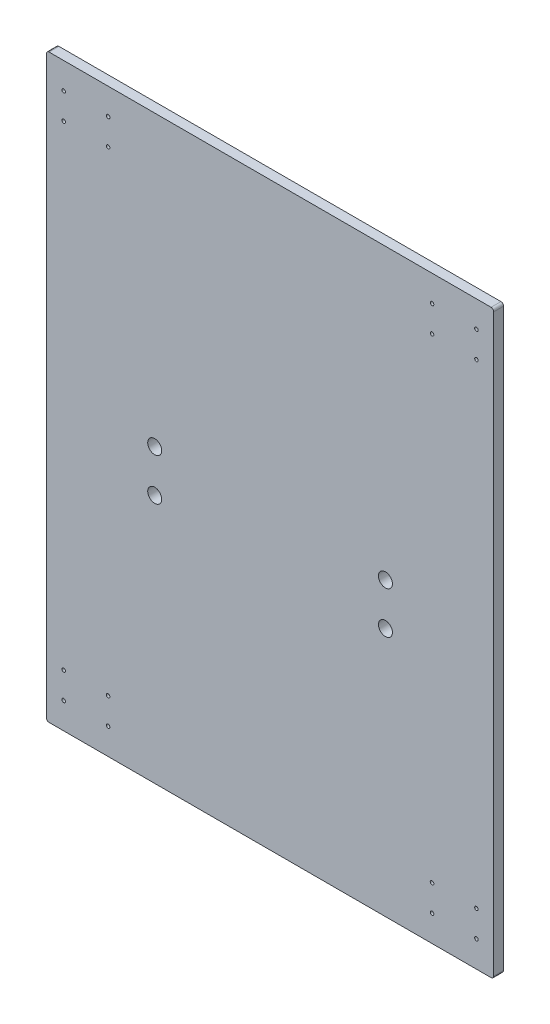
SolidWorks part; units mm, degrees
material "Plain Carbon Steel"
ref_plane "Front Plane" through (0, 0, 0) normal (0, 0, 1) x (1, 0, 0)
ref_plane "Top Plane" through (0, 0, 0) normal (0, 1, 0) x (1, 0, 0)
ref_plane "Right Plane" through (0, 0, 0) normal (1, 0, 0) x (0, 0, -1)
sketch "Sketch1" plane through (0, 0, 0) normal (0, 0, 1) x (1, 0, 0)
  line L1 (0, 0) -> (0, 38.1) construction
  line L2 (393.7, -522.3669) -> (-38.1, -522.3669)
  line L3 (393.7, -522.3669) -> (393.7, 38.1)
  line L4 (393.7, 38.1) -> (-38.1, 38.1)
  line L5 (-38.1, -522.3669) -> (-38.1, 38.1)
  line L6 (393.7, -522.3669) -> (-38.1, 38.1) construction
  line L7 (393.7, 38.1) -> (-38.1, -522.3669) construction
  line L9 (0, 0) -> (-38.1, 0) construction
  line L10 (-25.4, -21.4312) -> (-25.4, 21.4312) construction
  point P4 (177.8, -242.1334)
  dimension "D1" = 12.7
extrude "Boss-Extrude1" add sketch "Sketch1" along normal blind 9.525
fillet "Fillet1" radius 2.54 4 edges at (393.7, 38.1, 4.7625) (393.7, -522.3669, 4.7625) (-38.1, -522.3669, 4.7625) (-38.1, 38.1, 4.7625)
sketch "Sketch3" plane through (0, 0, 0) normal (0, 0, -1) x (-1, 0, 0)
  line L0 (-177.8, 38.1) -> (-177.8, -522.3669) construction
  line L1 (-391.16, 38.1) -> (35.56, 38.1) construction
  line L2 (35.56, -522.3669) -> (-391.16, -522.3669) construction
  line L3 (-177.8, -261.1431) -> (-289.1714, -261.1431) construction
  line L4 (-289.1714, -240.8231) -> (-289.1714, -281.4631) construction
  point P8 (-289.1714, -240.8231)
  point P9 (-289.1714, -281.4631)
  point P13 (-66.4286, -281.4631)
  point P14 (-66.4286, -240.8231)
  dimension "D1" = 40.64
  dimension "D2" = 240.9038
  dimension "D3" = 222.7428
hole_wizard "1/2 Clearance Hole1" positions "Sketch3" profile "Sketch4" hole size "1/2" standard "ANSI Inch" end condition up to next
sketch "Sketch4" plane through (66.4286, -240.8231, 0) normal (1, 0, 0) x (0, 1, 0)
  line L0 (0, 0) -> (0, 9.525)
  line L1 (0, 9.525) -> (6.7462, 9.525)
  line L2 (6.7462, 9.525) -> (6.7462, 0)
  line L5 (6.7462, 0) -> (0, 0)
  line L11 (0, -6.35) -> (0, 107.95) construction
  dimension "Thru Hole Dia." = 13.4925
  dimension "Thru Hole Depth" = 9.525
sketch "Sketch6" plane through (0, 0, 0) normal (0, 0, -1) x (-1, 0, 0)
  line L0 (-393.7, -519.8269) -> (-393.7, 35.56) construction
  line L1 (-391.16, 38.1) -> (35.56, 38.1) construction
  line L2 (-177.8, 38.1) -> (-177.8, -522.3669) construction
  line L3 (35.56, -522.3669) -> (-391.16, -522.3669) construction
  line L4 (38.1, -242.1334) -> (-393.7, -242.1334) construction
  line L5 (38.1, 35.56) -> (38.1, -519.8269) construction
  point P0 (-377.0376, 12.7)
  point P1 (-377.0376, -12.7)
  point P2 (-334.1624, 12.7)
  point P3 (-334.1624, -12.7)
  point P16 (-21.4376, -12.7)
  point P17 (21.4376, -12.7)
  point P18 (21.4376, 12.7)
  point P19 (-21.4376, 12.7)
  point P20 (-21.4376, -496.9669)
  point P21 (21.4376, -496.9669)
  point P22 (21.4376, -471.5669)
  point P23 (-21.4376, -471.5669)
  point P24 (-334.1624, -471.5669)
  point P25 (-334.1624, -496.9669)
  point P26 (-377.0376, -471.5669)
  point P27 (-377.0376, -496.9669)
  dimension "D1" = 16.6624
  dimension "D2" = 25.4
  dimension "D3" = 25.4
  dimension "D4" = 42.8752
hole_wizard "#5 Clearance Hole1" positions "Sketch6" profile "Sketch7" hole size "#5" standard "ANSI Inch" end condition up to next
sketch "Sketch7" plane through (377.0376, 12.7, 0) normal (1, 0, 0) x (0, 1, 0)
  line L0 (0, 0) -> (0, 9.525)
  line L1 (0, 9.525) -> (1.7272, 9.525)
  line L2 (1.7272, 9.525) -> (1.7272, 0)
  line L5 (1.7272, 0) -> (0, 0)
  line L11 (0, -6.35) -> (0, 107.95) construction
  dimension "Thru Hole Dia." = 3.4544
  dimension "Thru Hole Depth" = 9.525
